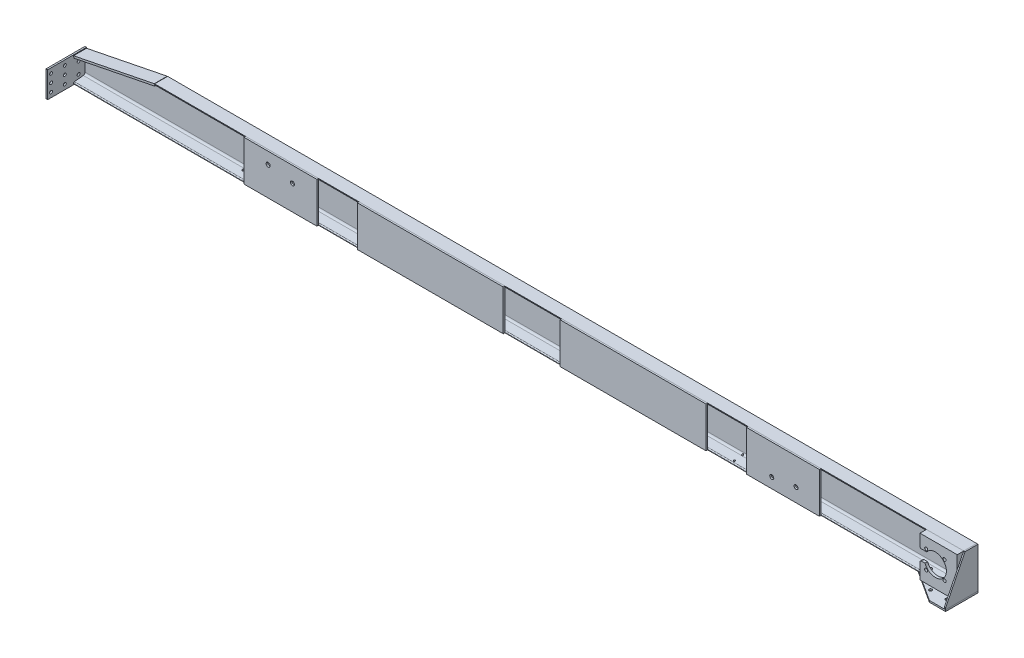
SolidWorks part; units mm, degrees
note: The reader was unsure of these and kept them because the rebuilt part matched: shared geometry of "草图26<2>".
other "EM010002"
other "EM010001"
material "普通碳钢"
ref_plane "前视基准面" through (0, 0, 0) normal (0, 0, 1) x (1, 0, 0)
ref_plane "上视基准面" through (0, 0, 0) normal (0, 1, 0) x (1, 0, 0)
ref_plane "右视基准面" through (0, 0, 0) normal (1, 0, 0) x (0, 0, -1)
sketch "草图1" plane through (0, 0, 0) normal (0, 0, 1) x (1, 0, 0)
  line L0 (-2745, 0) -> (2745, 0)
  dimension "D1" = 5490
other "槽钢 25B#(1)"
ref_plane "基准面1" through (-2745, 125, 0) normal (1, 0, 0) x (0, 0, 1)
sketch "草图114" plane through (-2745, 125, 0) normal (1, 0, 0) x (0, 0, 1)
  line L0 (0, -125) -> (80, -125)
  line L1 (80, -125) -> (80, -121.9796)
  line L2 (74.597, -116.0094) -> (19.8061, -110.5309)
  line L3 (9, -98.5904) -> (9, 98.5904)
  line L4 (19.8061, 110.5309) -> (74.597, 116.0094)
  line L5 (80, 121.9796) -> (80, 125)
  line L6 (80, 125) -> (0, 125)
  line L7 (0, 125) -> (0, -125)
  line L8 (44.5, 113) -> (44.5, -113) construction
  line L9 (0, 0) -> (9, 0) construction
  line L10 (44.5, 113) -> (44.5, 135) construction
  line L11 (44.5, 135) -> (80, 135) construction
  line L12 (80, 135) -> (80, 125) construction
  line L13 (44.5, 135) -> (9, 135) construction
  line L14 (9, 135) -> (9, 98.5904) construction
  arc A0 (19.8061, -110.5309) -> (9, -98.5904) centre (21, -98.5904) cw
  arc A1 (9, 98.5904) -> (19.8061, 110.5309) centre (21, 98.5904) cw
  arc A2 (80, -121.9796) -> (74.597, -116.0094) centre (74, -121.9796) ccw
  arc A3 (74.597, 116.0094) -> (80, 121.9796) centre (74, 121.9796) ccw
  point P2 (0, 0)
  point P19 (0, -125)
  point P20 (0, 125)
  point P22 (0, -125)
  point P23 (80, -125)
  point P24 (80, 125)
  point P26 (80, -116.5496)
  point P27 (21, 98.5904)
  point P28 (21, -98.5904)
  point P29 (80, 116.5496)
  dimension "D7" = 12
  dimension "D9" = 6
  dimension "D1" = 5.71
  dimension "D2" = 10
  dimension "D3" = 250
  dimension "D4" = 80
  dimension "D5" = 9
  dimension "D6" = 12
  dimension "D8" = 5.71
sketch "草图12" plane through (0, 0, 0) normal (0, 0, -1) x (-1, 0, 0)
  line L0 (2745, 250) -> (2745, 137.7624)
  line L1 (2745, 0) -> (2745, 250) construction
  line L2 (2745, 137.7624) -> (2245, 237.7624)
  line L4 (2245, 250) -> (2745, 250)
  line L5 (2745, 150) -> (2245, 250) construction
  line L8 (2305, 238) -> (2733, 238) construction
  line L9 (2733, 238) -> (2733, 152.4) construction
  line L10 (2733, 152.4) -> (2305, 238) construction
  line L11 (2245, 250) -> (2245, 237.7624)
  line L13 (2183.8118, 250) -> (2745, 250) construction
  line L14 (2745, 137.7624) -> (2183.8118, 250) construction
  dimension "D1" = 500
  dimension "D3" = 100
  dimension "D2" = 12
extrude "切除-拉伸1" cut sketch "草图12" against normal up to next
sketch "草图13" plane through (0, 0, 0) normal (0, 0, -1) x (-1, 0, 0)
  line L0 (2245, 237.7624) -> (2745, 137.7624) construction
  line L1 (2245, 237.7624) -> (2742.6466, 138.233)
  line L2 (2247.3534, 249.5293) -> (2245, 237.7624)
  line L4 (2249.8596, 249.0281) -> (2733, 152.4) construction
  line L5 (2247.3534, 249.5293) -> (2745, 150)
  line L6 (2745, 150) -> (2742.6466, 138.233)
  line L7 (2733, 152.4) -> (2733, 194.746) construction
  line L8 (2249.8596, 249.0281) -> (2249.8596, 249.0281) construction
  line L9 (2745, 137.7624) -> (2745, 194.746) construction
  line L10 (2245.054, 238.0323) -> (2245, 237.7624) construction
  line L11 (2745, 0) -> (2745, 137.7624) construction
  line L12 (2245, 237.7624) -> (2745, 137.7624) construction
  dimension "D1" = 12
extrude "凸台-拉伸1" add sketch "草图13" against normal up to surface (80 mm away) separate body up to face at (250, 248.4898, 80)
sketch "草图14" plane through (-2745, 0, 0) normal (-1, 0, 0) x (0, 0, 1)
  line L0 (80, 0) -> (0, 0) construction
  line L1 (0, -5) -> (240, -5)
  line L2 (0, -5) -> (0, 155)
  line L3 (0, 155) -> (240, 155)
  line L4 (240, -5) -> (240, 155)
  line L5 (80, 150) -> (0, 150) construction
  line L6 (0, 0) -> (0, 137.7624) construction
  dimension "D1" = 5
  dimension "D2" = 5
  dimension "D3" = 160
  dimension "D4" = 240
extrude "凸台-拉伸2" add sketch "草图14" along normal blind 10 separate body
sketch "草图15" plane through (0, 0, 80) normal (0, 0, 1) x (1, 0, 0)
  line L1 (-1685, 0) -> (-1235, 0)
  line L2 (-1685, 0) -> (-1685, 250)
  line L3 (-1685, 250) -> (-1235, 250)
  line L4 (-1235, 0) -> (-1235, 250)
  line L5 (2745, 250) -> (-2245, 250) construction
  line L7 (-985, 0) -> (-85, 0)
  line L8 (-985, 0) -> (-985, 250)
  line L9 (-985, 250) -> (-85, 250)
  line L10 (-85, 0) -> (-85, 250)
  line L11 (265, 0) -> (1165, 0)
  line L12 (265, 0) -> (265, 250)
  line L13 (265, 250) -> (1165, 250)
  line L14 (1165, 0) -> (1165, 250)
  line L15 (-2745, 137.7624) -> (-2745, 26.4096) construction
  line L16 (1415, 0) -> (1865, 0)
  line L17 (1415, 0) -> (1415, 250)
  line L18 (1415, 250) -> (1865, 250)
  line L19 (1865, 0) -> (1865, 250)
  line L21 (-2745, 0) -> (2745, 0) construction
  point P24 (-2745, 82.086)
  point P25 (1415, 125)
  dimension "D1" = 1060
  dimension "D2" = 450
  dimension "D3" = 250
  dimension "D4" = 2650
  dimension "D5" = 450
  dimension "D6" = 250
  dimension "D7" = 900
  dimension "D8" = 900
extrude "凸台-拉伸3" add sketch "草图15" along normal blind 10 separate body
sketch "草图16" plane through (0, 0, 0) normal (0, -1, 0) x (1, 0, 0)
  line L0 (2753, 0) -> (2453, 0)
  line L1 (-2745, 0) -> (2745, 0) construction
  line L2 (2453, 0) -> (2453, 70)
  line L4 (2453, 70) -> (2653, 200)
  line L5 (2653, 200) -> (2753, 200)
  line L6 (2753, 200) -> (2753, 0)
  line L7 (2745, 80) -> (2745, 0) construction
  dimension "D1" = 300
  dimension "D2" = 70
  dimension "D3" = 200
  dimension "D4" = 100
  dimension "D5" = 8
extrude "凸台-拉伸4" add sketch "草图16" along normal blind 10 separate body
sketch "草图17" plane through (2745, 0, 0) normal (1, 0, 0) x (0, 0, -1)
  line L0 (-80, 250) -> (0, 250)
  line L1 (0, 250) -> (0, 0)
  line L2 (0, 0) -> (-200, 0)
  line L3 (-200, 0) -> (-200, 10)
  line L4 (-200, 10) -> (-80, 250)
  dimension "D1" = 10
extrude "凸台-拉伸5" add sketch "草图17" along normal blind 8 separate body
sketch "草图18" plane through (0, 0, 90) normal (0, 0, 1) x (1, 0, 0)
  line L0 (-1685, 250) -> (-1685, 0) construction
  line L1 (-1235, 250) -> (-1685, 250) construction
  circle A0 centre (-1535, 178) radius 12.5
  circle A1 centre (-1385, 153) radius 12.5
  dimension "D1" = 150
  dimension "D2" = 25
  dimension "D3" = 25
  dimension "D4" = 150
  dimension "D5" = 72
  dimension "D6" = 25
extrude "切除-拉伸2" cut sketch "草图18" against normal up to surface (90 mm away)
sketch "草图19" plane through (0, 0, 90) normal (0, 0, 1) x (1, 0, 0)
  line L2 (2745, 250) -> (-2245, 250) construction
  circle A0 centre (1571, 63) radius 12.5
  circle A1 centre (1721, 84) radius 12.5
  circle A2 centre (-1535, 178) radius 12.5 construction
  dimension "D1" = 25
  dimension "D2" = 25
  dimension "D3" = 3106
  dimension "D4" = 187
  dimension "D5" = 150
  dimension "D6" = 21
extrude "切除-拉伸3" cut sketch "草图19" against normal up to surface (90 mm away)
sketch "草图20" plane through (0, 0, 0) normal (0, -1, 0) x (1, 0, 0)
  line L0 (2745, 80) -> (-2745, 80) construction
  line L1 (-1612, 80) -> (-1562, 80)
  line L2 (-1612, 80) -> (-1612, 9)
  line L3 (-1612, 9) -> (-1562, 9)
  line L4 (-1562, 80) -> (-1562, 9)
  line L5 (-2745, 0) -> (2745, 0) construction
  line L6 (-1535, 101.725) -> (-1535, 19.8207) construction
  point P11 (-1535, 60.7728)
  dimension "D1" = 12.5
  dimension "D2" = 27
  dimension "D3" = 50
  dimension "D4" = 9
extrude "切除-拉伸4" cut sketch "草图20" against normal up to vertex (26.4096 mm away) up to point (-2745, 26.4096, 9)
sketch "草图21" plane through (0, 0, 0) normal (0, -1, 0) x (1, 0, 0)
  line L0 (2745, 80) -> (-1562, 80) construction
  line L1 (1516, 80) -> (1696, 80)
  line L2 (1516, 80) -> (1516, 9)
  line L3 (1516, 9) -> (1696, 9)
  line L4 (1696, 80) -> (1696, 9)
  line L6 (1571, 95.9212) -> (1571, 8.0132) construction
  line L10 (2745, 9) -> (-1562, 9) construction
  dimension "D1" = 12.5
  dimension "D2" = 55
  dimension "D3" = 180
extrude "切除-拉伸5" cut sketch "草图21" against normal up to vertex (26.4096 mm away) contours L3 L4 L1 L2 up to point (-2745, 26.4096, 9)
sketch "草图22" plane through (-2755, 0, 0) normal (-1, 0, 0) x (0, 0, 1)
  line L0 (0, 75) -> (240, 75) construction
  line L1 (0, 155) -> (0, -5) construction
  line L2 (240, -5) -> (240, 155) construction
  line L3 (0, 25) -> (240, 25) construction
  line L4 (0, 125) -> (240, 125) construction
  line L5 (134, 155) -> (134, -5) construction
  line L6 (154, 155) -> (154, -5) construction
  line L8 (49, 155) -> (49, -5) construction
  line L9 (219, 155) -> (219, -5) construction
  line L10 (0, 105) -> (240, 105) construction
  line L11 (0, 35) -> (240, 35) construction
  line L12 (9, 137.7624) -> (9, 26.4096) construction
  circle A3 centre (134, 25) radius 9
  circle A4 centre (219, 25) radius 9
  circle A5 centre (219, 75) radius 9
  circle A6 centre (219, 125) radius 9
  circle A8 centre (134, 75) radius 9
  circle A9 centre (49, 105) radius 9
  circle A10 centre (49, 35) radius 9
  circle A13 centre (134, 125) radius 9
  dimension "D5" = 70
  dimension "D6" = 20
  dimension "D7" = 18
  dimension "D8" = 18
  dimension "D9" = 18
  dimension "D10" = 18
  dimension "D11" = 18
  dimension "D12" = 40
  dimension "D16" = 18
  dimension "D17" = 18
  dimension "D1" = 50
  dimension "D3" = 85
  dimension "D2" = 50
  dimension "D4" = 85
  dimension "D14" = 30
  dimension "D15" = 40
extrude "切除-拉伸6" cut sketch "草图22" against normal up to next (10 mm away)
sketch "草图23" plane through (0, 0, 80) normal (0, 0, 1) x (1, 0, 0)
  line L0 (2745, 250) -> (-2245, 250) construction
  line L1 (2745, 250) -> (2515, 250)
  line L2 (2745, 250) -> (2745, 0)
  line L3 (2745, 0) -> (2515, 0)
  line L4 (2515, 250) -> (2515, 0)
  line L5 (2745, 0) -> (1696, 0) construction
  line L6 (2610, 258) -> (2610, 0) construction
  line L7 (2745, 129) -> (2515, 129) construction
  line L8 (2745, 223.5904) -> (2745, 26.4096) construction
  line L9 (2610, 129) -> (2666.5685, 185.5685) construction
  line L10 (2610, 129) -> (2553.4315, 185.5685) construction
  line L11 (2610, 129) -> (2553.4315, 72.4315) construction
  line L12 (2610, 129) -> (2666.5685, 72.4315) construction
  circle A0 centre (2610, 129) radius 68
  circle A1 centre (2610, 129) radius 80 construction
  circle A2 centre (2553.4315, 185.5685) radius 9.5
  circle A3 centre (2666.5685, 185.5685) radius 9.5
  circle A4 centre (2666.5685, 72.4315) radius 9.5
  circle A5 centre (2553.4315, 72.4315) radius 9.5
  dimension "D2" = 136
  dimension "D3" = 160
  dimension "D8" = 19
  dimension "D9" = 19
  dimension "D10" = 19
  dimension "D11" = 19
  dimension "D1" = 230
  dimension "D4" = 45
  dimension "D5" = 45
  dimension "D6" = 45
  dimension "D7" = 45
  dimension "D12" = 95
  dimension "D13" = 121
extrude "凸台-拉伸6" add sketch "草图23" along normal blind 40 separate body
sketch "草图24" plane through (2515, 0, 0) normal (-1, 0, 0) x (0, 0, 1)
  line L0 (120, 138) -> (80, 138) construction
  line L1 (120, 250) -> (120, 0) construction
  line L2 (80, 250) -> (80, 0) construction
  line L3 (120, 250) -> (80, 250) construction
  line L4 (80, 170.5) -> (120, 170.5)
  line L5 (80, 170.5) -> (80, 105.5)
  line L6 (80, 105.5) -> (120, 105.5)
  line L7 (120, 170.5) -> (120, 105.5)
  dimension "D1" = 32.5
  dimension "D2" = 32.5
  dimension "D3" = 112
extrude "切除-拉伸7" cut sketch "草图24" against normal up to next
sketch "草图25" plane through (2515, 0, 0) normal (-1, 0, 0) x (0, 0, 1)
  line L0 (80, 250) -> (80, 170.5) construction
  line L1 (80, 240) -> (104, 240)
  line L2 (80, 240) -> (80, 10)
  line L3 (80, 10) -> (104, 10)
  line L4 (104, 240) -> (104, 10)
  line L5 (120, 250) -> (80, 250) construction
  line L6 (120, 0) -> (80, 0) construction
  dimension "D1" = 10
  dimension "D2" = 10
  dimension "D3" = 24
extrude "切除-拉伸8" cut sketch "草图25" against normal blind 220
fillet "圆角1" radius 20 2 edges at (2735, 10, 92) (2735, 240, 92)
fillet "圆角2" radius 10 2 edges at (2515, 105.5, 112) (2515, 170.5, 112)
sketch "草图26" plane through (0, 0, 0) normal (0, 1, 0) x (1, 0, 0)
  line L0 (2745, -140) -> (2578.6655, -140) construction
  line L1 (2745, -200) -> (2745, 0) construction
  line L2 (2743.2419, -40) -> (2457.063, -40) construction
  line L3 (2501, -14.6886) -> (2501, -136.0513) construction
  line L4 (2601, -14.6886) -> (2601, -200.3534) construction
  line L5 (2701, -20.2414) -> (2701, -309.7643) construction
  line L6 (2753, 0) -> (2753, -200) construction
  line L7 (2453, 0) -> (2753, 0) construction
  circle A0 centre (2601, -140) radius 9
  circle A1 centre (2701, -140) radius 9
  circle A2 centre (2701, -40) radius 9
  circle A3 centre (2601, -40) radius 9
  circle A4 centre (2501, -40) radius 9
  dimension "D6" = 18
  dimension "D7" = 18
  dimension "D8" = 18
  dimension "D9" = 18
  dimension "D10" = 18
  dimension "D1" = 52
  dimension "D2" = 100
  dimension "D3" = 100
  dimension "D4" = 40
  dimension "D5" = 100
extrude "切除-拉伸9" cut sketch "草图26" against normal up to next (10 mm away)
extrude "切除-拉伸11" cut sketch "草图26<2>" along normal up to surface (1.5511 mm away)
sketch "草图26<2>" plane through (0, 0, 0) normal (0, 1, 0) x (1, 0, 0) same geometry as "草图26"
sketch "草图27" plane through (0, 0, 0) normal (0, -1, 0) x (1, 0, 0)
  line L1 (2745, 0) -> (-2745, 0) construction
  line L2 (2745, 30) -> (-2745, 30) construction
  line L3 (1756, 0) -> (1756, 80) construction
  line L4 (1516, 80) -> (-1562, 80) construction
  line L6 (1799, 0) -> (1799, 80) construction
  line L7 (1713, 0) -> (1713, 80) construction
  line L8 (1696, 80) -> (1696, 9) construction
  circle A0 centre (1799, 30) radius 7
  circle A1 centre (1713, 30) radius 7
  dimension "D5" = 14
  dimension "D1" = 30
  dimension "D2" = 60
  dimension "D3" = 43
  dimension "D4" = 43
extrude "切除-拉伸12" cut sketch "草图27" against normal up to next
pattern_linear "阵列(线性)1" count 2 spacing 3460 along (-1, 0, 0) of "切除-拉伸12"
fillet "圆角3" radius 5 5 edges at (2615, 240, 104) (2729.1421, 234.1421, 104) (2735, 125, 104) (2615, 10, 104) (2729.1421, 15.8579, 104)
sketch "草图115" plane through (0, 0, 0) normal (0, -1, 0) x (1, 0, 0)
  line L0 (1416, 70.2624) -> (1416, 5.7971) construction
  line L1 (1316, 70.2624) -> (1316, 5.7971) construction
  line L2 (1430.683, 65) -> (1302.5505, 65) construction
  line L3 (1430.683, 15) -> (1302.5505, 15) construction
  line L4 (1516, 80) -> (1516, 9) construction
  line L5 (2745, 0) -> (-2745, 0) construction
  circle A0 centre (1316, 15) radius 5
  circle A1 centre (1316, 65) radius 5
  circle A2 centre (1416, 65) radius 5
  circle A3 centre (1416, 15) radius 5
  dimension "D1" = 10
  dimension "D2" = 100
  dimension "D3" = 100
  dimension "D4" = 50
  dimension "D5" = 15
extrude "切除-拉伸13" cut sketch "草图115" against normal up to next (105.5 mm away)
